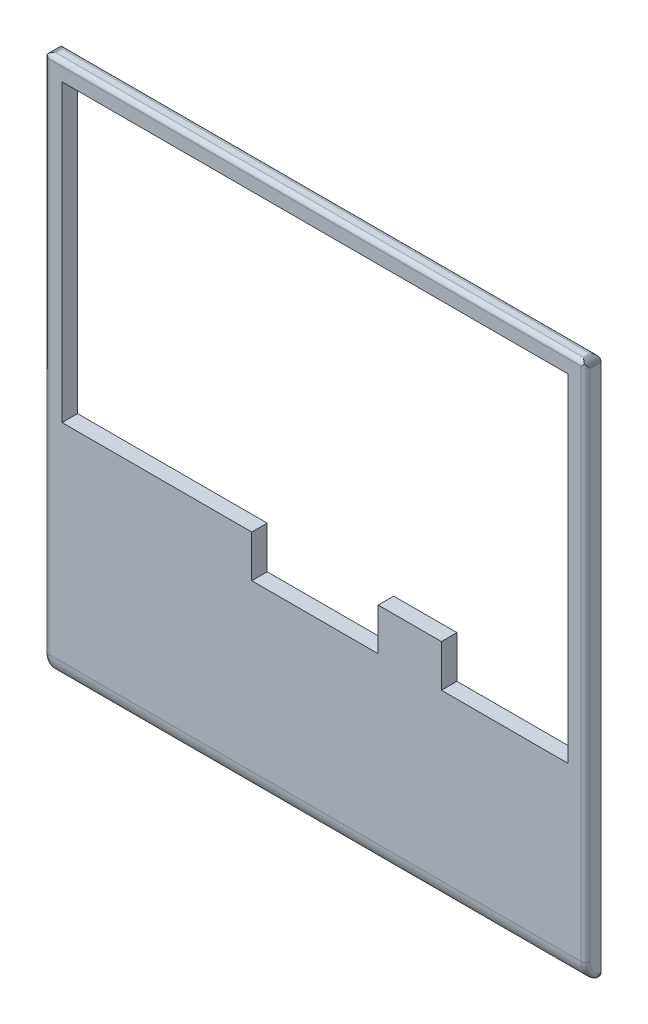
SolidWorks part; units mm, degrees
ref_plane "Front Plane" through (0, 0, 0) normal (0, 0, 1) x (1, 0, 0)
ref_plane "Top Plane" through (0, 0, 0) normal (0, 1, 0) x (1, 0, 0)
ref_plane "Right Plane" through (0, 0, 0) normal (1, 0, 0) x (0, 0, -1)
sketch "Model" plane through (0, 0, 0) normal (0, 0, 1) x (1, 0, 0)
  line L0 (241.697, 244.733) -> (241.931, 244.723)
  line L1 (241.931, 244.723) -> (242.165, 244.697)
  line L2 (242.165, 244.697) -> (242.397, 244.65)
  line L3 (242.397, 244.65) -> (242.623, 244.586)
  line L4 (242.623, 244.586) -> (242.845, 244.504)
  line L5 (242.845, 244.504) -> (243.057, 244.406)
  line L6 (243.057, 244.406) -> (243.264, 244.29)
  line L7 (243.264, 244.29) -> (243.459, 244.161)
  line L8 (243.459, 244.161) -> (243.644, 244.015)
  line L9 (243.644, 244.015) -> (243.818, 243.855)
  line L10 (243.818, 243.855) -> (243.978, 243.681)
  line L11 (243.978, 243.681) -> (244.124, 243.497)
  line L12 (244.124, 243.497) -> (244.253, 243.301)
  line L13 (244.253, 243.301) -> (244.369, 243.094)
  line L14 (244.369, 243.094) -> (244.468, 242.88)
  line L15 (244.468, 242.88) -> (244.549, 242.66)
  line L16 (244.549, 242.66) -> (244.613, 242.433)
  line L17 (244.613, 242.433) -> (244.66, 242.203)
  line L18 (244.66, 242.203) -> (244.686, 241.969)
  line L19 (244.686, 241.969) -> (244.697, 241.733)
  line L20 (244.697, 241.733) -> (244.697, 3.1309)
  line L21 (244.697, 3.1309) -> (244.686, 2.8966)
  line L22 (244.686, 2.8966) -> (244.66, 2.6624)
  line L23 (244.66, 2.6624) -> (244.613, 2.4309)
  line L24 (244.613, 2.4309) -> (244.549, 2.2049)
  line L25 (244.549, 2.2049) -> (244.468, 1.983)
  line L26 (244.468, 1.983) -> (244.369, 1.7708)
  line L27 (244.369, 1.7708) -> (244.253, 1.5641)
  line L28 (244.253, 1.5641) -> (244.124, 1.3684)
  line L29 (244.124, 1.3684) -> (243.978, 1.1837)
  line L30 (243.978, 1.1837) -> (243.818, 1.0101)
  line L31 (243.818, 1.0101) -> (243.644, 0.8503)
  line L32 (243.644, 0.8503) -> (243.459, 0.7042)
  line L33 (243.459, 0.7042) -> (243.264, 0.5746)
  line L34 (243.264, 0.5746) -> (243.057, 0.4589)
  line L35 (243.057, 0.4589) -> (242.845, 0.3597)
  line L36 (242.845, 0.3597) -> (242.623, 0.2784)
  line L37 (242.623, 0.2784) -> (242.397, 0.215)
  line L38 (242.397, 0.215) -> (242.165, 0.1681)
  line L39 (242.165, 0.1681) -> (241.931, 0.1419)
  line L40 (241.931, 0.1419) -> (241.697, 0.1309)
  line L41 (241.697, 0.1309) -> (3.0951, 0.1309)
  line L42 (3.0951, 0.1309) -> (2.8594, 0.1419)
  line L43 (2.8594, 0.1419) -> (2.6252, 0.1681)
  line L44 (2.6252, 0.1681) -> (2.395, 0.215)
  line L45 (2.395, 0.215) -> (2.1677, 0.2784)
  line L46 (2.1677, 0.2784) -> (1.9472, 0.3597)
  line L47 (1.9472, 0.3597) -> (1.7336, 0.4589)
  line L48 (1.7336, 0.4589) -> (1.5269, 0.5746)
  line L49 (1.5269, 0.5746) -> (1.3312, 0.7042)
  line L50 (1.3312, 0.7042) -> (1.1465, 0.8503)
  line L51 (1.1465, 0.8503) -> (0.9729, 1.0101)
  line L52 (0.9729, 1.0101) -> (0.813, 1.1837)
  line L53 (0.813, 1.1837) -> (0.667, 1.3684)
  line L54 (0.667, 1.3684) -> (0.5374, 1.5641)
  line L55 (0.5374, 1.5641) -> (0.4217, 1.7708)
  line L56 (0.4217, 1.7708) -> (0.3238, 1.983)
  line L57 (0.3238, 1.983) -> (0.2412, 2.2049)
  line L58 (0.2412, 2.2049) -> (0.1778, 2.4309)
  line L59 (0.1778, 2.4309) -> (0.1309, 2.6624)
  line L60 (0.1309, 2.6624) -> (0.1047, 2.8966)
  line L61 (0.1047, 2.8966) -> (0.0951, 3.1323)
  line L62 (0.0951, 3.1323) -> (0.0951, 241.733)
  line L63 (0.0951, 241.733) -> (0.1047, 241.969)
  line L64 (0.1047, 241.969) -> (0.1309, 242.203)
  line L65 (0.1309, 242.203) -> (0.1778, 242.433)
  line L66 (0.1778, 242.433) -> (0.2412, 242.66)
  line L67 (0.2412, 242.66) -> (0.3238, 242.88)
  line L68 (0.3238, 242.88) -> (0.4217, 243.094)
  line L69 (0.4217, 243.094) -> (0.5374, 243.301)
  line L70 (0.5374, 243.301) -> (0.667, 243.497)
  line L71 (0.667, 243.497) -> (0.813, 243.681)
  line L72 (0.813, 243.681) -> (0.9729, 243.855)
  line L73 (0.9729, 243.855) -> (1.1465, 244.015)
  line L74 (1.1465, 244.015) -> (1.3312, 244.161)
  line L75 (1.3312, 244.161) -> (1.5269, 244.29)
  line L76 (1.5269, 244.29) -> (1.7336, 244.406)
  line L77 (1.7336, 244.406) -> (1.9472, 244.504)
  line L78 (1.9472, 244.504) -> (2.1677, 244.586)
  line L79 (2.1677, 244.586) -> (2.395, 244.65)
  line L80 (2.395, 244.65) -> (2.6252, 244.697)
  line L81 (2.6252, 244.697) -> (2.8594, 244.723)
  line L82 (2.8594, 244.723) -> (3.0951, 244.733)
  line L83 (3.0951, 244.733) -> (241.697, 244.733)
  line L84 (3.7703, 5.1304) -> (3.4782, 4.9816)
  line L85 (3.4782, 4.9816) -> (3.2453, 4.7487)
  line L86 (3.2453, 4.7487) -> (3.0951, 4.4566)
  line L87 (3.0951, 4.4566) -> (3.0441, 4.1314)
  line L88 (3.0441, 4.1314) -> (3.0951, 3.8075)
  line L89 (3.0951, 3.8075) -> (3.2453, 3.514)
  line L90 (3.2453, 3.514) -> (3.4782, 3.2825)
  line L91 (3.4782, 3.2825) -> (3.7703, 3.1337)
  line L92 (3.7703, 3.1337) -> (4.0955, 3.0813)
  line L93 (4.0955, 3.0813) -> (4.4193, 3.1337)
  line L94 (4.4193, 3.1337) -> (4.7129, 3.2825)
  line L95 (4.7129, 3.2825) -> (4.9444, 3.514)
  line L96 (4.9444, 3.514) -> (5.0932, 3.8075)
  line L97 (5.0932, 3.8075) -> (5.1456, 4.1314)
  line L98 (5.1456, 4.1314) -> (5.0932, 4.4566)
  line L99 (5.0932, 4.4566) -> (4.9444, 4.7487)
  line L100 (4.9444, 4.7487) -> (4.7129, 4.9816)
  line L101 (4.7129, 4.9816) -> (4.4193, 5.1304)
  line L102 (4.4193, 5.1304) -> (4.0955, 5.1814)
  line L103 (4.0955, 5.1814) -> (3.7703, 5.1304)
  line L104 (82.6368, 5.1304) -> (82.3447, 4.9816)
  line L105 (82.3447, 4.9816) -> (82.1133, 4.7487)
  line L106 (82.1133, 4.7487) -> (81.963, 4.4566)
  line L107 (81.963, 4.4566) -> (81.9118, 4.1314)
  line L108 (81.9118, 4.1314) -> (81.963, 3.8075)
  line L109 (81.963, 3.8075) -> (82.1133, 3.514)
  line L110 (82.1133, 3.514) -> (82.3447, 3.2825)
  line L111 (82.3447, 3.2825) -> (82.6368, 3.1337)
  line L112 (82.6368, 3.1337) -> (82.962, 3.0813)
  line L113 (82.962, 3.0813) -> (83.2859, 3.1337)
  line L114 (83.2859, 3.1337) -> (83.5794, 3.2825)
  line L115 (83.5794, 3.2825) -> (83.8108, 3.514)
  line L116 (83.8108, 3.514) -> (83.9611, 3.8075)
  line L117 (83.9611, 3.8075) -> (84.0123, 4.1314)
  line L118 (84.0123, 4.1314) -> (83.9611, 4.4566)
  line L119 (83.9611, 4.4566) -> (83.8108, 4.7487)
  line L120 (83.8108, 4.7487) -> (83.5794, 4.9816)
  line L121 (83.5794, 4.9816) -> (83.2859, 5.1304)
  line L122 (83.2859, 5.1304) -> (82.962, 5.1814)
  line L123 (82.962, 5.1814) -> (82.6368, 5.1304)
  line L124 (161.505, 5.1304) -> (161.211, 4.9816)
  line L125 (161.211, 4.9816) -> (160.98, 4.7487)
  line L126 (160.98, 4.7487) -> (160.831, 4.4566)
  line L127 (160.831, 4.4566) -> (160.78, 4.1314)
  line L128 (160.78, 4.1314) -> (160.831, 3.8075)
  line L129 (160.831, 3.8075) -> (160.98, 3.514)
  line L130 (160.98, 3.514) -> (161.211, 3.2825)
  line L131 (161.211, 3.2825) -> (161.505, 3.1337)
  line L132 (161.505, 3.1337) -> (161.83, 3.0813)
  line L133 (161.83, 3.0813) -> (162.154, 3.1337)
  line L134 (162.154, 3.1337) -> (162.446, 3.2825)
  line L135 (162.446, 3.2825) -> (162.679, 3.514)
  line L136 (162.679, 3.514) -> (162.828, 3.8075)
  line L137 (162.828, 3.8075) -> (162.88, 4.1314)
  line L138 (162.88, 4.1314) -> (162.828, 4.4566)
  line L139 (162.828, 4.4566) -> (162.679, 4.7487)
  line L140 (162.679, 4.7487) -> (162.446, 4.9816)
  line L141 (162.446, 4.9816) -> (162.154, 5.1304)
  line L142 (162.154, 5.1304) -> (161.83, 5.1814)
  line L143 (161.83, 5.1814) -> (161.505, 5.1304)
  line L144 (240.371, 5.1304) -> (240.079, 4.9816)
  line L145 (240.079, 4.9816) -> (239.846, 4.7487)
  line L146 (239.846, 4.7487) -> (239.697, 4.4566)
  line L147 (239.697, 4.4566) -> (239.647, 4.1314)
  line L148 (239.647, 4.1314) -> (239.697, 3.8075)
  line L149 (239.697, 3.8075) -> (239.846, 3.514)
  line L150 (239.846, 3.514) -> (240.079, 3.2825)
  line L151 (240.079, 3.2825) -> (240.371, 3.1337)
  line L152 (240.371, 3.1337) -> (240.696, 3.0813)
  line L153 (240.696, 3.0813) -> (241.02, 3.1337)
  line L154 (241.02, 3.1337) -> (241.314, 3.2825)
  line L155 (241.314, 3.2825) -> (241.545, 3.514)
  line L156 (241.545, 3.514) -> (241.694, 3.8075)
  line L157 (241.694, 3.8075) -> (241.747, 4.1314)
  line L158 (241.747, 4.1314) -> (241.694, 4.4566)
  line L159 (241.694, 4.4566) -> (241.545, 4.7487)
  line L160 (241.545, 4.7487) -> (241.314, 4.9816)
  line L161 (241.314, 4.9816) -> (241.02, 5.1304)
  line L162 (241.02, 5.1304) -> (240.696, 5.1814)
  line L163 (240.696, 5.1814) -> (240.371, 5.1304)
  line L164 (3.7703, 83.9971) -> (3.4782, 83.8482)
  line L165 (3.4782, 83.8482) -> (3.2453, 83.6164)
  line L166 (3.2453, 83.6164) -> (3.0951, 83.3229)
  line L167 (3.0951, 83.3229) -> (3.0441, 82.9991)
  line L168 (3.0441, 82.9991) -> (3.0951, 82.6742)
  line L169 (3.0951, 82.6742) -> (3.2453, 82.3817)
  line L170 (3.2453, 82.3817) -> (3.4782, 82.1489)
  line L171 (3.4782, 82.1489) -> (3.7703, 82)
  line L172 (3.7703, 82) -> (4.0955, 81.9478)
  line L173 (4.0955, 81.9478) -> (4.4193, 82)
  line L174 (4.4193, 82) -> (4.7129, 82.1489)
  line L175 (4.7129, 82.1489) -> (4.9444, 82.3817)
  line L176 (4.9444, 82.3817) -> (5.0932, 82.6742)
  line L177 (5.0932, 82.6742) -> (5.1456, 82.9991)
  line L178 (5.1456, 82.9991) -> (5.0932, 83.3229)
  line L179 (5.0932, 83.3229) -> (4.9444, 83.6164)
  line L180 (4.9444, 83.6164) -> (4.7129, 83.8482)
  line L181 (4.7129, 83.8482) -> (4.4193, 83.9971)
  line L182 (4.4193, 83.9971) -> (4.0955, 84.0493)
  line L183 (4.0955, 84.0493) -> (3.7703, 83.9971)
  line L184 (240.371, 83.9971) -> (240.079, 83.8482)
  line L185 (240.079, 83.8482) -> (239.846, 83.6164)
  line L186 (239.846, 83.6164) -> (239.697, 83.3229)
  line L187 (239.697, 83.3229) -> (239.647, 82.998)
  line L188 (239.647, 82.998) -> (239.697, 82.6742)
  line L189 (239.697, 82.6742) -> (239.846, 82.3817)
  line L190 (239.846, 82.3817) -> (240.079, 82.1489)
  line L191 (240.079, 82.1489) -> (240.371, 82)
  line L192 (240.371, 82) -> (240.696, 81.9478)
  line L193 (240.696, 81.9478) -> (241.02, 82)
  line L194 (241.02, 82) -> (241.314, 82.1489)
  line L195 (241.314, 82.1489) -> (241.545, 82.3817)
  line L196 (241.545, 82.3817) -> (241.694, 82.6742)
  line L197 (241.694, 82.6742) -> (241.747, 82.998)
  line L198 (241.747, 82.998) -> (241.694, 83.3229)
  line L199 (241.694, 83.3229) -> (241.545, 83.6164)
  line L200 (241.545, 83.6164) -> (241.314, 83.8482)
  line L201 (241.314, 83.8482) -> (241.02, 83.9971)
  line L202 (241.02, 83.9971) -> (240.696, 84.0479)
  line L203 (240.696, 84.0479) -> (240.371, 83.9971)
  line L204 (8.0932, 236.735) -> (8.0932, 103.382)
  line L205 (8.0932, 103.382) -> (93.8195, 103.382)
  line L206 (93.8195, 103.382) -> (93.8195, 84.3319)
  line L207 (93.8195, 84.3319) -> (150.971, 84.3319)
  line L208 (150.971, 84.3319) -> (150.971, 103.382)
  line L209 (150.971, 103.382) -> (179.544, 103.382)
  line L210 (179.544, 103.382) -> (179.544, 84.3319)
  line L211 (179.544, 84.3319) -> (236.696, 84.3319)
  line L212 (236.696, 84.3319) -> (236.696, 236.735)
  line L213 (236.696, 236.735) -> (8.0932, 236.735)
  line L214 (3.7703, 162.865) -> (3.4782, 162.715)
  line L215 (3.4782, 162.715) -> (3.2453, 162.483)
  line L216 (3.2453, 162.483) -> (3.0951, 162.191)
  line L217 (3.0951, 162.191) -> (3.0441, 161.866)
  line L218 (3.0441, 161.866) -> (3.0951, 161.542)
  line L219 (3.0951, 161.542) -> (3.2453, 161.248)
  line L220 (3.2453, 161.248) -> (3.4782, 161.017)
  line L221 (3.4782, 161.017) -> (3.7703, 160.867)
  line L222 (3.7703, 160.867) -> (4.0955, 160.816)
  line L223 (4.0955, 160.816) -> (4.4193, 160.867)
  line L224 (4.4193, 160.867) -> (4.7129, 161.017)
  line L225 (4.7129, 161.017) -> (4.9444, 161.248)
  line L226 (4.9444, 161.248) -> (5.0932, 161.542)
  line L227 (5.0932, 161.542) -> (5.1456, 161.866)
  line L228 (5.1456, 161.866) -> (5.0932, 162.191)
  line L229 (5.0932, 162.191) -> (4.9444, 162.483)
  line L230 (4.9444, 162.483) -> (4.7129, 162.715)
  line L231 (4.7129, 162.715) -> (4.4193, 162.865)
  line L232 (4.4193, 162.865) -> (4.0955, 162.916)
  line L233 (4.0955, 162.916) -> (3.7703, 162.865)
  line L234 (240.371, 162.865) -> (240.079, 162.715)
  line L235 (240.079, 162.715) -> (239.846, 162.483)
  line L236 (239.846, 162.483) -> (239.697, 162.191)
  line L237 (239.697, 162.191) -> (239.647, 161.866)
  line L238 (239.647, 161.866) -> (239.697, 161.542)
  line L239 (239.697, 161.542) -> (239.846, 161.248)
  line L240 (239.846, 161.248) -> (240.079, 161.017)
  line L241 (240.079, 161.017) -> (240.371, 160.867)
  line L242 (240.371, 160.867) -> (240.696, 160.816)
  line L243 (240.696, 160.816) -> (241.02, 160.867)
  line L244 (241.02, 160.867) -> (241.314, 161.017)
  line L245 (241.314, 161.017) -> (241.545, 161.248)
  line L246 (241.545, 161.248) -> (241.694, 161.542)
  line L247 (241.694, 161.542) -> (241.747, 161.866)
  line L248 (241.747, 161.866) -> (241.694, 162.191)
  line L249 (241.694, 162.191) -> (241.545, 162.483)
  line L250 (241.545, 162.483) -> (241.314, 162.715)
  line L251 (241.314, 162.715) -> (241.02, 162.865)
  line L252 (241.02, 162.865) -> (240.696, 162.916)
  line L253 (240.696, 162.916) -> (240.371, 162.865)
  line L254 (240.371, 241.733) -> (240.079, 241.583)
  line L255 (240.079, 241.583) -> (239.846, 241.35)
  line L256 (239.846, 241.35) -> (239.697, 241.058)
  line L257 (239.697, 241.058) -> (239.647, 240.732)
  line L258 (239.647, 240.732) -> (239.697, 240.409)
  line L259 (239.697, 240.409) -> (239.846, 240.115)
  line L260 (239.846, 240.115) -> (240.079, 239.883)
  line L261 (240.079, 239.883) -> (240.371, 239.735)
  line L262 (240.371, 239.735) -> (240.696, 239.682)
  line L263 (240.696, 239.682) -> (241.02, 239.735)
  line L264 (241.02, 239.735) -> (241.314, 239.883)
  line L265 (241.314, 239.883) -> (241.545, 240.115)
  line L266 (241.545, 240.115) -> (241.694, 240.409)
  line L267 (241.694, 240.409) -> (241.747, 240.732)
  line L268 (241.747, 240.732) -> (241.694, 241.058)
  line L269 (241.694, 241.058) -> (241.545, 241.35)
  line L270 (241.545, 241.35) -> (241.314, 241.583)
  line L271 (241.314, 241.583) -> (241.02, 241.733)
  line L272 (241.02, 241.733) -> (240.696, 241.782)
  line L273 (240.696, 241.782) -> (240.371, 241.733)
  line L274 (161.505, 241.733) -> (161.211, 241.583)
  line L275 (161.211, 241.583) -> (160.98, 241.35)
  line L276 (160.98, 241.35) -> (160.831, 241.058)
  line L277 (160.831, 241.058) -> (160.78, 240.732)
  line L278 (160.78, 240.732) -> (160.831, 240.409)
  line L279 (160.831, 240.409) -> (160.98, 240.115)
  line L280 (160.98, 240.115) -> (161.211, 239.883)
  line L281 (161.211, 239.883) -> (161.505, 239.735)
  line L282 (161.505, 239.735) -> (161.83, 239.682)
  line L283 (161.83, 239.682) -> (162.154, 239.735)
  line L284 (162.154, 239.735) -> (162.446, 239.883)
  line L285 (162.446, 239.883) -> (162.679, 240.115)
  line L286 (162.679, 240.115) -> (162.828, 240.409)
  line L287 (162.828, 240.409) -> (162.88, 240.732)
  line L288 (162.88, 240.732) -> (162.828, 241.058)
  line L289 (162.828, 241.058) -> (162.679, 241.35)
  line L290 (162.679, 241.35) -> (162.446, 241.583)
  line L291 (162.446, 241.583) -> (162.154, 241.733)
  line L292 (162.154, 241.733) -> (161.83, 241.782)
  line L293 (161.83, 241.782) -> (161.505, 241.733)
  line L294 (82.6368, 241.733) -> (82.3447, 241.583)
  line L295 (82.3447, 241.583) -> (82.1133, 241.35)
  line L296 (82.1133, 241.35) -> (81.963, 241.058)
  line L297 (81.963, 241.058) -> (81.9118, 240.732)
  line L298 (81.9118, 240.732) -> (81.963, 240.409)
  line L299 (81.963, 240.409) -> (82.1133, 240.115)
  line L300 (82.1133, 240.115) -> (82.3447, 239.883)
  line L301 (82.3447, 239.883) -> (82.6368, 239.735)
  line L302 (82.6368, 239.735) -> (82.962, 239.682)
  line L303 (82.962, 239.682) -> (83.2859, 239.735)
  line L304 (83.2859, 239.735) -> (83.5794, 239.883)
  line L305 (83.5794, 239.883) -> (83.8108, 240.115)
  line L306 (83.8108, 240.115) -> (83.9611, 240.409)
  line L307 (83.9611, 240.409) -> (84.0123, 240.732)
  line L308 (84.0123, 240.732) -> (83.9611, 241.058)
  line L309 (83.9611, 241.058) -> (83.8108, 241.35)
  line L310 (83.8108, 241.35) -> (83.5794, 241.583)
  line L311 (83.5794, 241.583) -> (83.2859, 241.733)
  line L312 (83.2859, 241.733) -> (82.962, 241.782)
  line L313 (82.962, 241.782) -> (82.6368, 241.733)
  line L314 (3.7703, 241.733) -> (3.4782, 241.583)
  line L315 (3.4782, 241.583) -> (3.2453, 241.35)
  line L316 (3.2453, 241.35) -> (3.0951, 241.058)
  line L317 (3.0951, 241.058) -> (3.0441, 240.734)
  line L318 (3.0441, 240.734) -> (3.0951, 240.409)
  line L319 (3.0951, 240.409) -> (3.2453, 240.115)
  line L320 (3.2453, 240.115) -> (3.4782, 239.883)
  line L321 (3.4782, 239.883) -> (3.7703, 239.735)
  line L322 (3.7703, 239.735) -> (4.0955, 239.684)
  line L323 (4.0955, 239.684) -> (4.4193, 239.735)
  line L324 (4.4193, 239.735) -> (4.7129, 239.883)
  line L325 (4.7129, 239.883) -> (4.9444, 240.115)
  line L326 (4.9444, 240.115) -> (5.0932, 240.409)
  line L327 (5.0932, 240.409) -> (5.1456, 240.734)
  line L328 (5.1456, 240.734) -> (5.0932, 241.058)
  line L329 (5.0932, 241.058) -> (4.9444, 241.35)
  line L330 (4.9444, 241.35) -> (4.7129, 241.583)
  line L331 (4.7129, 241.583) -> (4.4193, 241.733)
  line L332 (4.4193, 241.733) -> (4.0955, 241.784)
  line L333 (4.0955, 241.784) -> (3.7703, 241.733)
  point P334 (0, 0)
extrude "凸台-拉伸1" add sketch "Model" along normal blind 7 contours L102 L103 L84 L85 L86 L87 L88 L89 L90 L91 L92 L93 L94 L95 L96 L97 L98 L99 L100 L101 | L83 L82 L81 L80 L79 L78 L77 L76 L75 L74 L73 L72 L71 L70 L69 L68 L67 L66 L65 L64 L63 L62 L61 L60 L59 L58 L57 L56 L55 L54 L53 L52 L51 L50 L49 L48 L47 L46 L45 L44 L43 L42 L41 L40 L39 L38 L37 L36 L35 L34 L33 | L122 L123 L104 L105 L106 L107 L108 L109 L110 L111 L112 L113 L114 L115 L116 L117 L118 L119 L120 L121 | L142 L143 L124 L125 L126 L127 L128 L129 L130 L131 L132 L133 L134 L135 L136 L137 L138 L139 L140 L141 | L162 L163 L144 L145 L146 L147 L148 L149 L150 L151 L152 L153 L154 L155 L156 L157 L158 L159 L160 L161 | L202 L203 L184 L185 L186 L187 L188 L189 L190 L191 L192 L193 L194 L195 L196 L197 L198 L199 L200 L201 | L252 L253 L234 L235 L236 L237 L238 L239 L240 L241 L242 L243 L244 L245 L246 L247 L248 L249 L250 L251 | L272 L273 L254 L255 L256 L257 L258 L259 L260 L261 L262 L263 L264 L265 L266 L267 L268 L269 L270 L271 | L292 L293 L274 L275 L276 L277 L278 L279 L280 L281 L282 L283 L284 L285 L286 L287 L288 L289 L290 L291 | L312 L313 L294 L295 L296 L297 L298 L299 L300 L301 L302 L303 L304 L305 L306 L307 L308 L309 L310 L311 | L332 L333 L314 L315 L316 L317 L318 L319 L320 L321 L322 L323 L324 L325 L326 L327 L328 L329 L330 L331 | L232 L233 L214 L215 L216 L217 L218 L219 L220 L221 L222 L223 L224 L225 L226 L227 L228 L229 L230 L231 | L182 L183 L164 L165 L166 L167 L168 L169 L170 L171 L172 L173 L174 L175 L176 L177 L178 L179 L180 L181 region at (118.9561, 71.1889, 0) region at (4.0947, 4.1318, 0) region at (82.962, 4.1318, 0) region at (161.8295, 4.1318, 0) region at (240.6959, 4.1318, 0) region at (4.0947, 82.9986, 0) region at (240.6959, 82.9985, 0) region at (4.0947, 161.866, 0) region at (240.6959, 161.866, 0) region at (240.6959, 240.7331, 0) region at (161.8295, 240.7331, 0) region at (82.962, 240.7331, 0) region at (4.0947, 240.7335, 0)
fillet "圆角2" radius 10 1 edges at (122.396, 0.1309, 7)
fillet "圆角4" radius 2 8 edges at (244.697, 6.1814, 6.3716) (0.0951, 6.1822, 6.3719) (241.697, 244.733, 3.5) (122.396, 244.733, 7) (3.0951, 244.733, 3.5) (122.396, 244.733, 0) (244.697, 125.7017, 7) (0.0951, 125.7017, 7)
sketch "草图2" plane through (0, 0, 0) normal (0, 0, -1) x (-1, 0, 0)
  line L0 (-241.747, 4.1314) -> (-239.647, 4.1314) construction
  line L1 (-84.0123, 4.1314) -> (-81.9118, 4.1314) construction
  line L2 (-5.1456, 4.1314) -> (-3.0441, 4.1314) construction
  line L3 (-5.1456, 82.9991) -> (-3.0441, 82.9991) construction
  line L4 (-5.1456, 161.866) -> (-3.0441, 161.866) construction
  line L5 (-5.1456, 240.734) -> (-3.0441, 240.734) construction
  line L6 (-84.0123, 240.732) -> (-81.9118, 240.732) construction
  line L7 (-162.88, 240.732) -> (-160.78, 240.732) construction
  line L8 (-241.747, 240.732) -> (-239.647, 240.732) construction
  line L9 (-241.747, 161.866) -> (-239.647, 161.866) construction
  line L10 (-241.747, 82.998) -> (-239.647, 82.998) construction
  circle A0 centre (-240.697, 4.1314) radius 1.45
  circle A1 centre (-161.8335, 4.1314) radius 1.45
  circle A2 centre (-82.9621, 4.1314) radius 1.45
  circle A3 centre (-4.0948, 4.1314) radius 1.45
  circle A4 centre (-4.0948, 82.9991) radius 1.45
  circle A5 centre (-4.0948, 161.866) radius 1.45
  circle A6 centre (-4.0948, 240.734) radius 1.45
  circle A7 centre (-82.9621, 240.732) radius 1.45
  circle A8 centre (-161.83, 240.732) radius 1.45
  circle A9 centre (-240.697, 240.732) radius 1.45
  circle A10 centre (-240.697, 161.866) radius 1.45
  circle A11 centre (-240.697, 82.998) radius 1.45
extrude "切除-拉伸1" cut sketch "草图2" against normal blind 3
